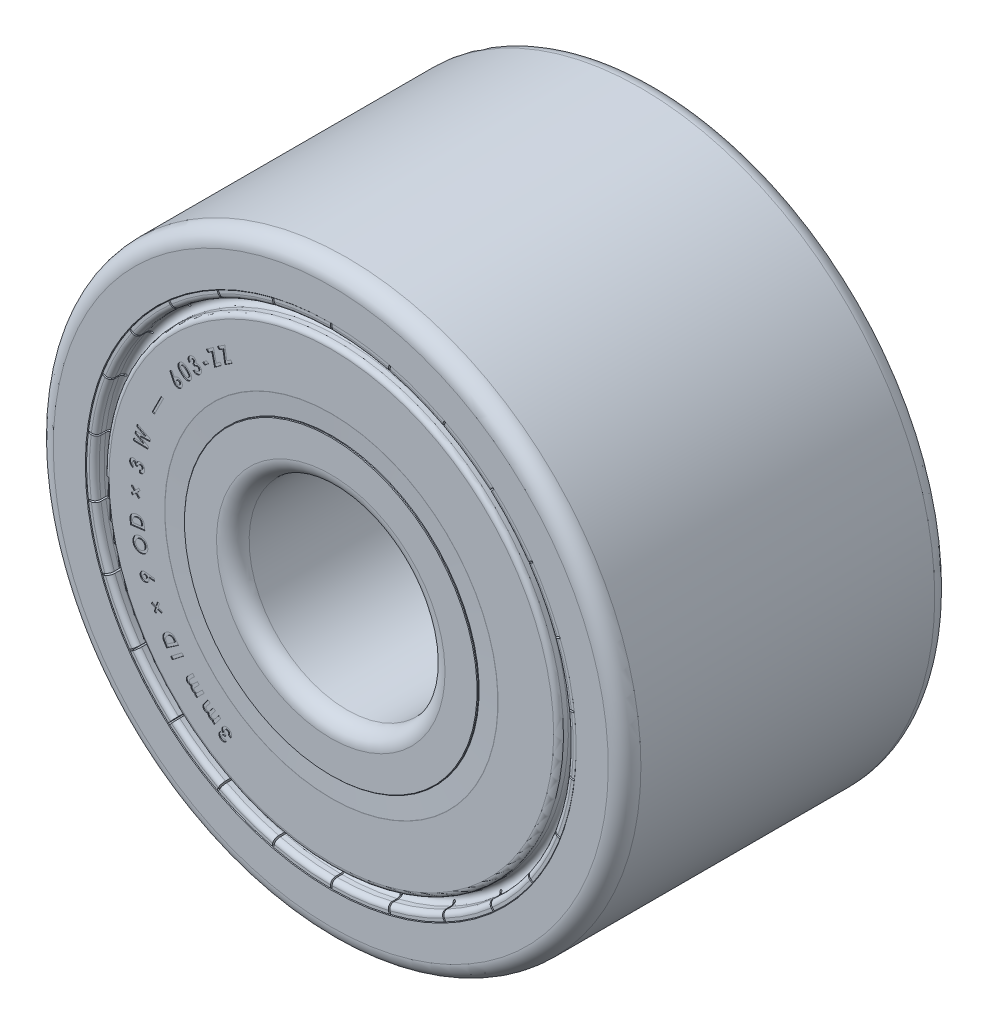
SolidWorks part; units mm, degrees
note: The reader was unsure of these and kept them because the rebuilt part matched: shared geometry of "Sketch F, SLIT SEED<2>".
material "AISI 316 Annealed Stainless Steel Bar (SS)"
ref_plane "Front" through (0, 0, 0) normal (0, 0, 1) x (1, 0, 0)
ref_plane "Top" through (0, 0, 0) normal (0, 1, 0) x (1, 0, 0)
ref_plane "Right" through (0, 0, 0) normal (1, 0, 0) x (0, 0, -1)
sketch "LAYOUT R" plane through (0, 0, 0) normal (1, 0, 0) x (0, 0, -1)
  line L0 (-2.25, 1.5) -> (2.25, 1.5)
  line L1 (2.5, -4.5) -> (-2.5, -4.5) construction
  line L2 (2.5, -4.5) -> (2.5, 2.5781) construction
  line L3 (2.25, 4.5) -> (-2.25, 4.5)
  line L4 (-2.5, -4.5) -> (-2.5, 4.25) construction
  line L6 (2.6982, 0) -> (-2.6982, 0) construction
  line L7 (-2.491, 2.25) -> (2.491, 2.25)
  line L8 (-2.491, 3.75) -> (2.491, 3.75)
  line L11 (-8.89, 0) -> (8.89, 0) construction
  line L12 (-2.5, 4.25) -> (-2.5, 3.759)
  line L13 (2.5, 4.25) -> (2.5, 3.759)
  line L16 (-2.5, 2.241) -> (-2.5, 1.75)
  line L17 (2.5, 2.241) -> (2.5, 1.75)
  line L30 (-2.491, 3.75) -> (-2.491, 2.25) construction
  line L31 (2.491, 3.75) -> (2.491, 2.25) construction
  line L32 (-2.491, 2.55) -> (2.491, 2.55) construction
  line L33 (-2.4909, 2.55) -> (-2.4778, 2.25)
  line L34 (2.4909, 2.55) -> (2.4778, 2.25)
  line L35 (-2.491, 3.63) -> (2.491, 3.63) construction
  line L38 (-2.5, 3.759) -> (2.5, 3.759) construction
  line L39 (-2.491, 3.75) -> (-2.491, 3.705)
  line L40 (-2.416, 3.63) -> (-2.341, 3.63)
  line L41 (-2.491, 2.5533) -> (-2.491, 3.405)
  line L42 (-2.416, 3.48) -> (-2.341, 3.48)
  line L43 (2.491, 2.5533) -> (2.491, 3.405)
  line L44 (2.416, 3.48) -> (2.341, 3.48)
  line L45 (2.416, 3.63) -> (2.341, 3.63)
  line L46 (-2.491, 3.48) -> (2.491, 3.48) construction
  line L50 (-1.3199, 3.45) -> (1.3199, 3.45) construction
  line L53 (2.491, 2.25) -> (2.5, 2.241)
  line L54 (-2.491, 2.25) -> (-2.5, 2.241)
  line L56 (-2.5, 2.241) -> (2.5, 2.241) construction
  line L57 (2.5, 3.759) -> (2.491, 3.75) construction
  line L58 (2.5, 3.759) -> (2.491, 3.75)
  line L60 (-2.5, 3.759) -> (-2.491, 3.75) construction
  line L61 (-2.5, 3.759) -> (-2.491, 3.75)
  line L64 (-2.341, 3.48) -> (-2.341, 3.63) construction
  line L65 (2.341, 3.48) -> (2.341, 3.63) construction
  line L66 (2.491, 3.75) -> (2.491, 3.705)
  arc A2 (-2.416, 3.48) -> (-2.491, 3.405) centre (-2.416, 3.405) ccw
  arc A3 (2.491, 3.405) -> (2.416, 3.48) centre (2.416, 3.405) ccw
  arc A4 (2.4909, 2.55) -> (2.491, 2.5533) centre (2.416, 2.5533) ccw
  arc A5 (-2.491, 2.5533) -> (-2.4909, 2.55) centre (-2.416, 2.5533) ccw
  arc A6 (-2.341, 3.48) -> (-2.341, 3.63) centre (-2.341, 3.555) ccw
  arc A7 (2.341, 3.63) -> (2.341, 3.48) centre (2.341, 3.555) ccw
  arc A8 (-2.25, 4.5) -> (-2.5, 4.25) centre (-2.25, 4.25) ccw
  arc A9 (-2.5, 1.75) -> (-2.25, 1.5) centre (-2.25, 1.75) ccw
  arc A10 (2.25, 1.5) -> (2.5, 1.75) centre (2.25, 1.75) ccw
  arc A11 (-2.491, 3.705) -> (-2.416, 3.63) centre (-2.416, 3.705) ccw
  arc A12 (2.416, 3.63) -> (2.491, 3.705) centre (2.416, 3.705) ccw
  arc A13 (2.5, 4.25) -> (2.25, 4.5) centre (2.25, 4.25) ccw
  point P0 (0, 0)
  point P7 (-2.25, 4.5)
  point P8 (-2.416, 3.63)
  point P15 (0, 0)
  point P29 (-2.491, 3.705)
  point P38 (-2.4909, 2.55)
  point P54 (-2.491, 3.405)
  point P55 (-2.416, 3.48)
  point P56 (-2.491, 3.405)
  point P58 (-2.491, 2.5533)
  point P59 (-2.4909, 2.55)
  point P60 (2.416, 3.48)
  point P62 (2.491, 3.405)
  point P63 (2.491, 2.5533)
  point P64 (2.4909, 2.55)
  point P71 (-2.5, 4.25)
  point P72 (-2.5, 1.75)
  point P73 (-2.25, 1.5)
  point P74 (2.25, 1.5)
  point P75 (2.5, 1.75)
  point P80 (2.25, 4.5)
  point P81 (2.416, 3.63)
  point P88 (2.491, 3.705)
  point P91 (2.5, 4.25)
  dimension "D21" = 0.15
  dimension "D33" = 0.25
  dimension "D3" = 1.5
  dimension "D4" = 2.25
  dimension "D5" = 3.75
  dimension "D24" = 5
  dimension "D6" = 4.991
  dimension "D7" = 4.991
  dimension "D11" = 0.3
  dimension "D12" = 2.5
  dimension "D13" = 2.5
  dimension "D14" = 0.12
  dimension "D17" = 0.009
  dimension "D18" = 0.15
  dimension "D19" = 0.15
  dimension "D20" = 0.15
  dimension "D15" = 0.3
  dimension "D23" = 45
  dimension "D25" = 45
  dimension "D27" = 0.009
  dimension "D28" = 4.5
  dimension "D29" = 5
  dimension "D30" = 9
  dimension "D8" = 2.5
  dimension "D31" = 45
  dimension "D32" = 45
sketch "Sketch R, INNER BODY" plane through (0, 0, 0) normal (1, 0, 0) x (0, 0, -1)
  line L1 (-2.491, 2.25) -> (-2.5, 2.241) construction
  line L3 (-2.5, 2.241) -> (-2.5, 1.75) construction
  line L12 (-8.89, 0) -> (8.89, 0) construction
  line L13 (-8.89, 0) -> (8.89, 0) construction
  line L14 (-2.25, 1.5) -> (2.25, 1.5) construction
  line L15 (2.5, 2.241) -> (2.5, 1.75) construction
  line L16 (2.491, 2.25) -> (2.5, 2.241) construction
  line L17 (-2.491, 2.25) -> (2.491, 2.25) construction
  line L18 (-2.491, 2.25) -> (-2.5, 2.241)
  line L19 (-2.5, 2.241) -> (-2.5, 1.75)
  line L20 (-2.25, 1.5) -> (2.25, 1.5)
  line L21 (2.5, 2.241) -> (2.5, 1.75)
  line L22 (2.491, 2.25) -> (2.5, 2.241)
  line L23 (-2.491, 2.25) -> (2.491, 2.25)
  arc A0 (-2.5, 1.75) -> (-2.25, 1.5) centre (-2.25, 1.75) ccw construction
  arc A1 (2.25, 1.5) -> (2.5, 1.75) centre (2.25, 1.75) ccw construction
  arc A2 (-2.5, 1.75) -> (-2.25, 1.5) centre (-2.25, 1.75) ccw
  arc A3 (2.25, 1.5) -> (2.5, 1.75) centre (2.25, 1.75) ccw
sketch "Sketch R, OUTER BODY" plane through (0, 0, 0) normal (1, 0, 0) x (0, 0, -1)
  line L8 (-8.89, 0) -> (8.89, 0) construction
  line L9 (-8.89, 0) -> (8.89, 0) construction
  line L31 (-2.5, 4.25) -> (-2.5, 3.759) construction
  line L84 (-2.5, 3.759) -> (-2.491, 3.75) construction
  line L85 (-2.491, 3.75) -> (2.491, 3.75) construction
  line L86 (2.5, 3.759) -> (2.491, 3.75) construction
  line L87 (2.5, 4.25) -> (2.5, 3.759) construction
  line L88 (2.25, 4.5) -> (-2.25, 4.5) construction
  line L89 (-2.5, 4.25) -> (-2.5, 3.759)
  line L90 (-2.5, 3.759) -> (-2.491, 3.75)
  line L91 (-2.491, 3.75) -> (2.491, 3.75)
  line L92 (2.5, 3.759) -> (2.491, 3.75)
  line L93 (2.5, 4.25) -> (2.5, 3.759)
  line L94 (2.25, 4.5) -> (-2.25, 4.5)
  arc A6 (2.5, 4.25) -> (2.25, 4.5) centre (2.25, 4.25) ccw construction
  arc A7 (-2.25, 4.5) -> (-2.5, 4.25) centre (-2.25, 4.25) ccw construction
  arc A8 (2.5, 4.25) -> (2.25, 4.5) centre (2.25, 4.25) ccw
  arc A9 (-2.25, 4.5) -> (-2.5, 4.25) centre (-2.25, 4.25) ccw
sketch "Sketch R, SHIELD FACES" plane through (0, 0, 0) normal (1, 0, 0) x (0, 0, -1)
  line L0 (-8.89, 0) -> (8.89, 0) construction
  line L1 (-8.89, 0) -> (8.89, 0) construction
  line L29 (-2.491, 3.75) -> (-2.491, 3.705) construction
  line L32 (-2.416, 3.63) -> (-2.341, 3.63) construction
  line L34 (-2.416, 3.48) -> (-2.341, 3.48) construction
  line L36 (-2.491, 2.5533) -> (-2.491, 3.405) construction
  line L38 (-2.4909, 2.55) -> (-2.4778, 2.25) construction
  line L39 (-2.491, 2.25) -> (2.491, 2.25) construction
  line L40 (2.4909, 2.55) -> (2.4778, 2.25) construction
  line L43 (2.491, 2.5533) -> (2.491, 3.405) construction
  line L79 (2.416, 3.48) -> (2.341, 3.48) construction
  line L80 (2.416, 3.63) -> (2.341, 3.63) construction
  line L81 (2.491, 3.75) -> (2.491, 3.705) construction
  line L82 (-2.491, 3.75) -> (2.491, 3.75) construction
  line L83 (-2.491, 3.75) -> (-2.491, 3.705)
  line L84 (-2.416, 3.63) -> (-2.341, 3.63)
  line L85 (-2.416, 3.48) -> (-2.341, 3.48)
  line L86 (-2.491, 2.5533) -> (-2.491, 3.405)
  line L87 (-2.4909, 2.55) -> (-2.4778, 2.25)
  line L88 (-2.4778, 2.25) -> (2.4778, 2.25)
  line L89 (2.4909, 2.55) -> (2.4778, 2.25)
  line L90 (2.491, 2.5533) -> (2.491, 3.405)
  line L91 (2.416, 3.48) -> (2.341, 3.48)
  line L92 (2.416, 3.63) -> (2.341, 3.63)
  line L93 (2.491, 3.75) -> (2.491, 3.705)
  line L94 (-2.491, 3.75) -> (2.491, 3.75)
  arc A28 (-2.491, 3.705) -> (-2.416, 3.63) centre (-2.416, 3.705) ccw construction
  arc A29 (-2.341, 3.48) -> (-2.341, 3.63) centre (-2.341, 3.555) ccw construction
  arc A30 (-2.416, 3.48) -> (-2.491, 3.405) centre (-2.416, 3.405) ccw construction
  arc A31 (2.491, 3.405) -> (2.416, 3.48) centre (2.416, 3.405) ccw construction
  arc A32 (2.341, 3.63) -> (2.341, 3.48) centre (2.341, 3.555) ccw construction
  arc A33 (2.416, 3.63) -> (2.491, 3.705) centre (2.416, 3.705) ccw construction
  arc A34 (-2.491, 3.705) -> (-2.416, 3.63) centre (-2.416, 3.705) ccw
  arc A35 (-2.341, 3.48) -> (-2.341, 3.63) centre (-2.341, 3.555) ccw
  arc A36 (-2.416, 3.48) -> (-2.491, 3.405) centre (-2.416, 3.405) ccw
  arc A37 (2.491, 3.405) -> (2.416, 3.48) centre (2.416, 3.405) ccw
  arc A38 (2.341, 3.63) -> (2.341, 3.48) centre (2.341, 3.555) ccw
  arc A39 (2.416, 3.63) -> (2.491, 3.705) centre (2.416, 3.705) ccw
  arc A40 (-2.491, 2.5533) -> (-2.4909, 2.55) centre (-2.416, 2.5533) ccw construction
  arc A41 (-2.491, 2.5533) -> (-2.4909, 2.55) centre (-2.416, 2.5533) ccw
  arc A42 (2.4909, 2.55) -> (2.491, 2.5533) centre (2.416, 2.5533) ccw construction
  arc A43 (2.4909, 2.55) -> (2.491, 2.5533) centre (2.416, 2.5533) ccw
revolve "Revolve INNER BODY" add sketch "Sketch R, INNER BODY" angle 360 about L13
revolve "Revolve OUTER BODY" add sketch "Sketch R, OUTER BODY" angle 360 about L9
revolve "Revolve SHIELDS" add sketch "Sketch R, SHIELD FACES" angle 360 about L1
sketch "Sketch TEXT RADIUS 1 — MANUALLY ASSIGN TEXT AND FONT SIZE (FROM EQUATIONS)" plane through (0, 0, 2.491) normal (0, 0, 1) x (1, 0, 0)
  circle A0 centre (0, 0) radius 2.89 construction
  text T0 "<b>3mm ID × 9 OD × 3 W  —  603-ZZ</b>" font "Century Gothic" height 0.22
  dimension "D1" = 5.78
extrude "Cut-Extrude LABEL 1" cut sketch "Sketch TEXT RADIUS 1 — MANUALLY ASSIGN TEXT AND FONT SIZE (FROM EQUATIONS)" against normal blind 0.0127
sketch "Sketch TEXT RADIUS 2 — MANUALLY ASSIGN TEXT AND FONT SIZE (FROM EQUATIONS)" plane through (0, 0, -2.491) normal (0, 0, -1) x (-1, 0, 0)
  circle A0 centre (0, 0) radius 2.89 construction
  text T0 "<b>3mm ID × 9 OD × 3 W  —  603-ZZ</b>" font "Century Gothic" height 0.22
  dimension "D1" = 5.78
extrude "Cut-Extrude LABEL 2" cut sketch "Sketch TEXT RADIUS 2 — MANUALLY ASSIGN TEXT AND FONT SIZE (FROM EQUATIONS)" against normal blind 0.0127
sketch "LAYOUT F, SLIT SEED" plane through (0, 0, 0) normal (0, 0, 1) x (1, 0, 0)
  line L0 (0, 0) -> (0, 12.7) construction
  line L3 (0.012, 3.75) -> (0.012, 3.6134)
  line L4 (-0.012, 3.75) -> (-0.012, 3.6134)
  circle A4 centre (0, 0) radius 3.6
  circle A5 centre (0, 0) radius 3.75
  circle A6 centre (0, 3.6) radius 0.018
  point P13 (-0.012, 3.75)
  point P15 (0.012, 3.75)
  dimension "D1" = 7.5
  dimension "D2" = 7.2
  dimension "D3" = 0.036
  dimension "D4" = 0.012
sketch "Sketch F, SLIT SEED" plane through (0, 0, 2.491) normal (0, 0, 1) x (1, 0, 0)
  line L1 (0.012, 3.75) -> (0.012, 3.6134) construction
  line L8 (-0.012, 3.75) -> (-0.012, 3.6134) construction
  line L9 (0.012, 3.75) -> (0.012, 3.6134)
  line L10 (-0.012, 3.75) -> (-0.012, 3.6134)
  circle A1 centre (0, 3.6) radius 0.018 construction
  circle A8 centre (0, 0) radius 3.75 construction
  arc A9 (-0.012, 3.6134) -> (0.012, 3.6134) centre (0, 3.6) ccw
  arc A10 (0.012, 3.75) -> (-0.012, 3.75) centre (0, 0) ccw
extrude "Cut-Extrude SLIT SEED F" cut sketch "Sketch F, SLIT SEED" along normal blind 0.635 from surface at -4.982 starting at face at (2.9102, 0.7811, -2.491)
extrude "Cut-Extrude SLIT SEED B" cut sketch "Sketch F, SLIT SEED<2>" against normal blind 0.635
sketch "Sketch F, SLIT SEED<2>" plane through (0, 0, 2.491) normal (0, 0, 1) x (1, 0, 0) same geometry as "Sketch F, SLIT SEED"
pattern_circular "CirPattern1" count 26 over 360 about axis through (0, 0, 0) along (0, 0, 1) of "Cut-Extrude SLIT SEED F"
pattern_circular "CirPattern2" count 26 over 360 about axis through (0, 0, 0) along (0, 0, 1) of "Cut-Extrude SLIT SEED B"
equation "\"_i__BORE\"= 3"
equation "\"_i__OUTSIDE_DIAMETER\"= 9"
equation "\"_i__WIDTH\"= 5"
equation "\"_user_applied_FONT_SIZE\"= int ( \"BODY_SPAN__SHIELD__OF_RADIUS\" * \"g_param__FONT_SIZE_RATIO\" * 100 ) / 100'MANUALLY ASSIGN TO FONT"
equation "\"BODY__HALF_WIDTH\"= \"_i__WIDTH\" / 2"
equation "\"BODY_SPAN___OF_DIAMETER\"= \"_i__OUTSIDE_DIAMETER\" - \"_i__BORE\""
equation "\"BODY_SPAN___OF_RADIUS\"= \"BODY_SPAN___OF_DIAMETER\" / 2"
equation "\"BODY_SPAN__BORE_AND_OD__OF RADIUS\"= ( \"BODY_SPAN___OF_RADIUS\" - \"BODY_SPAN__SHIELD__OF_RADIUS\" ) / 2"
equation "\"BODY_SPAN__SHIELD__OF_RADIUS\"= \"BODY_SPAN___OF_RADIUS\" * \"g_param__SHIELD_PANEL_SPAN__RATIO_OF_BODY_RADIAN\""
equation "\"BORE__RADIUS\"= \"_i__BORE\" / 2"
equation "\"CORNER_RADII\"= \"_i__WIDTH\" * \"g_param__CORNER_RADII__RATIO_TO_WIDTH\""
equation "\"OUTSIDE_RADIUS\"= \"_i__OUTSIDE_DIAMETER\" / 2"
equation "\"RING_INNER__OUTSIDE_RADIUS\"= \"BORE__RADIUS\" + \"BODY_SPAN__BORE_AND_OD__OF RADIUS\""
equation "\"RING_OUTER__INSIDE_DIAMETER\"= \"RING_OUTER__INSIDE_RADIUS\" * 2"
equation "\"RING_OUTER__INSIDE_RADIUS\"= ( \"_i__OUTSIDE_DIAMETER\" / 2 ) - \"BODY_SPAN__BORE_AND_OD__OF RADIUS\""
equation "\"SHIELD__BOTTOM_AND_TOP_REGIONS_SPAN\"= \"BODY_SPAN__SHIELD__OF_RADIUS\" * \"g_param__SHIELD__TOP_AND_BOTTOM_REGIONS_RATIO\""
equation "\"SHIELD__COMPRESSION_FILLET_DIAMETER\"= \"BODY_SPAN__SHIELD__OF_RADIUS\" * \"g_param__SHIELD_COMPRESSION_FILLET_DIAMETER_RATIO\""
equation "\"SHIELD__COMPRESSION_FILLET_RADIUS\"= \"SHIELD__COMPRESSION_FILLET_DIAMETER\" / 2"
equation "\"SHIELD__FACE_FILLET_DIAMETER\"= \"BODY_SPAN__SHIELD__OF_RADIUS\" * \"g_param__SHIELD_FACE_FILLET_RATIO\""
equation "\"SHIELD__FACE_INSET\"= \"SIDE_FACE_CHAMFERS\""
equation "\"SHIELD__FACE_TO_OPPOSING_BRG_BODY_FACE\"= \"_i__WIDTH\" - \"SHIELD__FACE_INSET\""
equation "\"SHIELD__HALF_SLIT_WIDTH\"= \"SHIELD__SLIT_WIDTH\" / 2"
equation "\"SHIELD__HALF_WALL\"= \"SHIELD__WALL\" / 2"
equation "\"SHIELD__SLIT_WIDTH\"= \"SHIELD__WALL\" / 5"
equation "\"SHIELD__WALL\"= \"BODY_SPAN__SHIELD__OF_RADIUS\" * \"g_param__SHIELD_WALL_TO_SPAN_RATIO\""
equation "\"SHIELD_SLIT__INSIDE_TERMINUS__DIAMETER\"= \"RING_OUTER__INSIDE_DIAMETER\" - \"SHIELD__BOTTOM_AND_TOP_REGIONS_SPAN\""
equation "\"SHIELD_SLIT__KEYHOLE_DIAMETER\"= \"SHIELD__SLIT_WIDTH\" * 1.5"
equation "\"SIDE_FACE_CHAMFERS\"= \"_i__OUTSIDE_DIAMETER\" * \"g_param__SIDE_CHAMFERS__RATIO_TO_OD\""
equation "\"TEXT_RADIUS\"= \"_i__BORE\" + ( \"BODY_SPAN___OF_DIAMETER\" / 2 ) - \"_user_applied_FONT_SIZE\""
equation "\"WIDTH__HALF\"= \"_i__WIDTH\" / 2"
equation "\"D1@CirPattern1\" = \"g_param__SHIELD__NUMBER_OF_SLITS\""
equation "\"D1@CirPattern2\" = \"g_param__SHIELD__NUMBER_OF_SLITS\""
equation "\"D1@LAYOUT F, SLIT SEED\"=\"RING_OUTER__INSIDE_DIAMETER\""
equation "\"D1@Sketch TEXT RADIUS 1 — MANUALLY ASSIGN TEXT AND FONT SIZE (FROM EQUATIONS)\" = \"TEXT_RADIUS\""
equation "\"D1@Sketch TEXT RADIUS 2 — MANUALLY ASSIGN TEXT AND FONT SIZE (FROM EQUATIONS)\" = \"TEXT_RADIUS\""
equation "\"D11@LAYOUT R\"=\"SHIELD__BOTTOM_AND_TOP_REGIONS_SPAN\""
equation "\"D12@LAYOUT R\" = \"g_param__SHIELD__INSIDE_BEVEL_ANGLE__DEGREES\""
equation "\"D13@LAYOUT R\"= \"g_param__SHIELD__INSIDE_BEVEL_ANGLE__DEGREES\""
equation "\"D14@LAYOUT R\"=\"SHIELD__WALL\""
equation "\"D15@LAYOUT R\"=\"SHIELD__BOTTOM_AND_TOP_REGIONS_SPAN\""
equation "\"D17@LAYOUT R\"=\"SIDE_FACE_CHAMFERS\""
equation "\"D18@LAYOUT R\"=\"SHIELD__COMPRESSION_FILLET_DIAMETER\""
equation "\"D19@LAYOUT R\"=\"SHIELD__COMPRESSION_FILLET_DIAMETER\""
equation "\"D2@LAYOUT F, SLIT SEED\"=\"SHIELD_SLIT__INSIDE_TERMINUS__DIAMETER\""
equation "\"D20@LAYOUT R\"=\"SHIELD__COMPRESSION_FILLET_DIAMETER\""
equation "\"D21@LAYOUT R\"=\"SHIELD__FACE_FILLET_DIAMETER\""
equation "\"D24@LAYOUT R\"=\"_i__WIDTH\""
equation "\"D27@LAYOUT R\"=\"SIDE_FACE_CHAMFERS\""
equation "\"D28@LAYOUT R\"=\"OUTSIDE_RADIUS\""
equation "\"D3@LAYOUT F, SLIT SEED\"=\"SHIELD_SLIT__KEYHOLE_DIAMETER\""
equation "\"D3@LAYOUT R\"=\"BORE__RADIUS\""
equation "\"D30@LAYOUT R\"=\"_i__OUTSIDE_DIAMETER\""
equation "\"D33@LAYOUT R\"=\"CORNER_RADII\""
equation "\"D4@LAYOUT F, SLIT SEED\"=\"SHIELD__HALF_SLIT_WIDTH\""
equation "\"D4@LAYOUT R\"=\"RING_INNER__OUTSIDE_RADIUS\""
equation "\"D5@LAYOUT F, SLIT SEED\"=\"SHIELD__HALF_SLIT_WIDTH\""
equation "\"D5@LAYOUT R\"=\"RING_OUTER__INSIDE_RADIUS\""
equation "\"D6@LAYOUT R\"=\"SHIELD__FACE_TO_OPPOSING_BRG_BODY_FACE\""
equation "\"D7@LAYOUT R\"=\"SHIELD__FACE_TO_OPPOSING_BRG_BODY_FACE\""
equation "\"D8@LAYOUT R\"=\"WIDTH__HALF\""
equation "\"g_param__CORNER_RADII__RATIO_TO_WIDTH\"= 0.05'ISO MAX IS 0.07 WHERE WIDTH IS LESS THAN DIAMETER"
equation "\"g_param__FONT_SIZE_RATIO\"= 0.15'EXPRESSES RADIAL PROPORTION OF SHIELD FACE"
equation "\"g_param__INDICIA__EXTRUSION_DEPTH\"=0.013'CONCAVE-EMBOSSED INDICIA ON SHIELD FACES"
equation "\"g_param__SHIELD__INSIDE_BEVEL_ANGLE__DEGREES\"= 2.5'SHOULD BE GREATER THAN 0 AND LESS THAN OR EQUAL TO 10, ORIGINALLY 1"
equation "\"g_param__SHIELD__NUMBER_OF_SLITS\"=26'OPTIONAL NUMBER OF SHIELD COMPRESSION RING SLITS"
equation "\"g_param__SHIELD__TOP_AND_BOTTOM_REGIONS_RATIO\"=0.2'PART OF RADIAL SHIELD SPAN OCCUPIED BY INMOST BEVEL, ORIGINALLY 0.2"
equation "\"g_param__SHIELD_COMPRESSION_FILLET_DIAMETER_RATIO\"=0.1'ORIGINALLY 0,1"
equation "\"g_param__SHIELD_FACE_FILLET_RATIO\"=0.1'ORIGINALLY 0.1"
equation "\"g_param__SHIELD_FACE_INSET__RATIO_OF_WIDTH\"= 0.035'ISO-UNSPECIFIED, SHOULD BE AT LEAST 0.025 and LESS THAN 0.036"
equation "\"g_param__SHIELD_PANEL_SPAN__RATIO_OF_BODY_RADIAN\"= 0.5'ISO-UNSPECIFIED, ORIGINALLY 0.5"
equation "\"g_param__SHIELD_WALL_TO_SPAN_RATIO\"=0.08'SHOULD BE LESS THAN 0.015, ORIGINALLY 0.08, PRESCRIBES MATERIAL THICKNESS"
equation "\"g_param__SIDE_CHAMFERS__RATIO_TO_OD\"= 0.001'NOT ISO-SPECIFIED"
